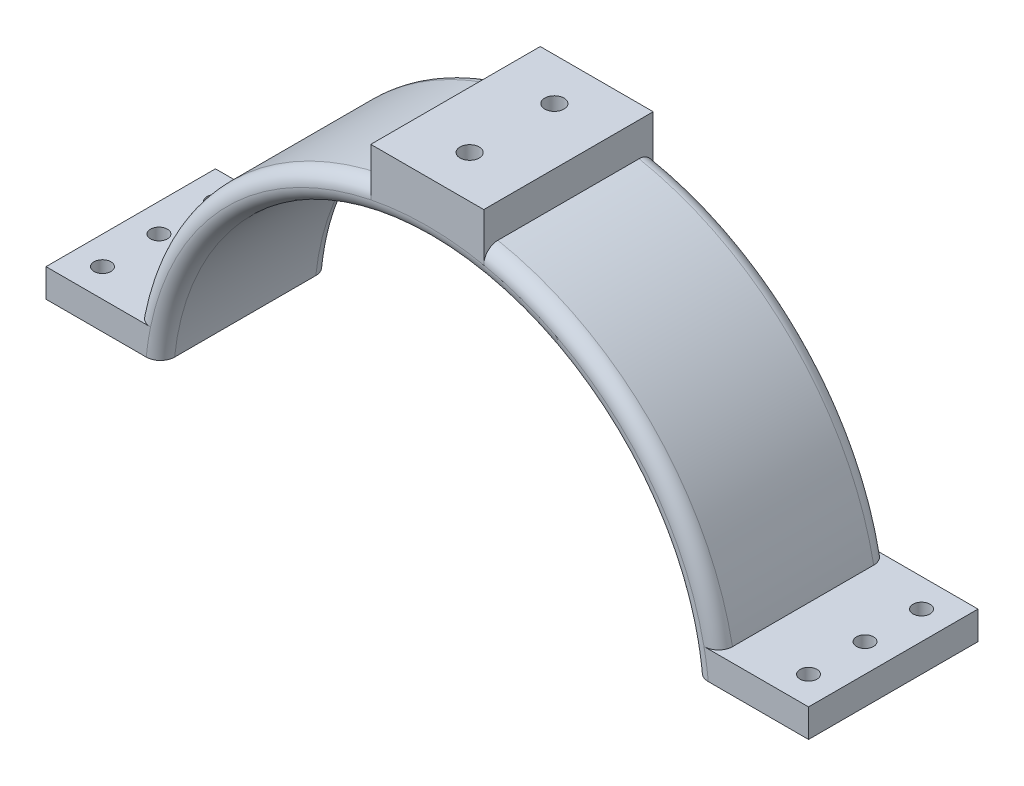
SolidWorks part; units mm, degrees
ref_plane "Front Plane" through (0, 0, 0) normal (0, 0, 1) x (1, 0, 0)
ref_plane "Top Plane" through (0, 0, 0) normal (0, 1, 0) x (1, 0, 0)
ref_plane "Right Plane" through (0, 0, 0) normal (1, 0, 0) x (0, 0, -1)
sketch "Sketch1" plane through (0, 0, 0) normal (0, 0, 1) x (1, 0, 0)
  line L0 (47.2361, 5) -> (67.5, 5)
  line L3 (-67.5, 5) -> (-47.2361, 5)
  line L6 (-10, 57.5) -> (10, 57.5)
  line L9 (-51.5388, 10) -> (-67.5, 10)
  line L10 (-67.5, 5) -> (-67.5, 10)
  line L13 (51.5388, 10) -> (67.5, 10)
  line L14 (67.5, 5) -> (67.5, 10)
  line L15 (-10, 57.5) -> (-10, 51.5388)
  line L17 (10, 57.5) -> (10, 51.5388)
  arc A2 (47.2361, 5) -> (-47.2361, 5) centre (0, 0) ccw
  arc A3 (51.5388, 10) -> (10, 51.5388) centre (0, 0) ccw
  arc A4 (-10, 51.5388) -> (-51.5388, 10) centre (0, 0) ccw
  dimension "D1" = 5
  dimension "D2" = 94.4722
  dimension "D8" = 5.9612
  dimension "D3" = 5
  dimension "D4" = 15.9612
  dimension "D5" = 15.9612
  dimension "D6" = 20.2639
  dimension "D7" = 20.2639
  dimension "D9" = 20
extrude "Boss-Extrude1" add sketch "Sketch1" along normal blind 30
fillet "Fillet1" radius 2.5 6 edges at (37.1231, 37.1231, 0) (0, 47.5, 0) (-37.1231, 37.1231, 0) (-37.1231, 37.1231, 30) (37.1231, 37.1231, 30) (0, 47.5, 30)
sketch "Sketch6" plane through (0, 5, 0) normal (0, -1, 0) x (1, 0, 0)
  line L0 (-47.2361, 2.5) -> (47.2361, 2.5) construction
  circle A0 centre (0, 22.5) radius 3.75
  circle A1 centre (0, 7.5) radius 3.75
  dimension "D1" = 7.5
  dimension "D2" = 7.5
  dimension "D3" = 15
  dimension "D4" = 5
extrude "Cut-Extrude1" cut sketch "Sketch6" against normal blind 47.5
hole_wizard "CSK for M3 Flat Head Machine Screw1" positions "Sketch7" profile "Sketch8" countersink size "M3" standard "ANSI Metric" end condition through all
sketch "Sketch7" plane through (0, 52.5, 0) normal (0, -1, 0) x (-1, 0, 0)
  point P0 (0, -22.5)
  point P3 (0, -7.5)
sketch "Sketch8" plane through (0, 52.5, 22.5) normal (1, 0, 0) x (0, 0, -1)
  line L0 (0, 0) -> (0, 5)
  line L1 (0, 5) -> (1.7, 5)
  line L2 (1.7, 5) -> (1.7, 1.45)
  line L3 (1.7, 1.45) -> (3.15, 0)
  line L5 (3.15, 0) -> (0, 0)
  line L6 (-1.7, 1.45) -> (-3.15, 0) construction
  line L11 (0, -6.35) -> (0, 107.95) construction
  dimension "Thru Hole Dia." = 3.4
  dimension "Thru Hole Depth" = 5
  dimension "Near C'Sink Dia." = 6.3
  dimension "Near C'Sink Angle" = 90
hole_wizard "Ø3.0mm Dowel Hole1" positions "Sketch9" profile "Sketch10" hole size "Ø3.0" standard "ANSI Metric" end condition through all
sketch "Sketch9" plane through (0, 10, 0) normal (0, 1, 0) x (1, 0, 0)
  line L0 (-48.9898, 0) -> (-67.5, 0) construction
  line L1 (-48.9898, -30) -> (-67.5, -30) construction
  line L2 (67.5, 0) -> (48.9898, 0) construction
  line L3 (-67.5, -30) -> (-67.5, 0) construction
  line L4 (67.5, -30) -> (67.5, 0) construction
  line L5 (67.5, -30) -> (48.9898, -30) construction
  point P0 (-62.5, -5)
  point P2 (-62.5, -15)
  point P4 (-62.5, -25)
  point P6 (62.5, -5)
  point P8 (62.5, -15)
  point P10 (62.5, -25)
  dimension "D1" = 5
  dimension "D2" = 15
  dimension "D3" = 5
  dimension "D4" = 5
  dimension "D5" = 5
  dimension "D6" = 5
  dimension "D7" = 5
  dimension "D8" = 5
  dimension "D9" = 5
  dimension "D10" = 5
  dimension "D11" = 15
  dimension "D12" = 5
sketch "Sketch10" plane through (-62.5, 10, 5) normal (1, 0, 0) x (0, 0, 1)
  line L0 (0, 0) -> (0, 5)
  line L1 (0, 5) -> (1.5, 5)
  line L2 (1.5, 5) -> (1.5, 0)
  line L5 (1.5, 0) -> (0, 0)
  line L11 (0, -6.35) -> (0, 107.95) construction
  dimension "Thru Hole Dia." = 3
  dimension "Thru Hole Depth" = 5
